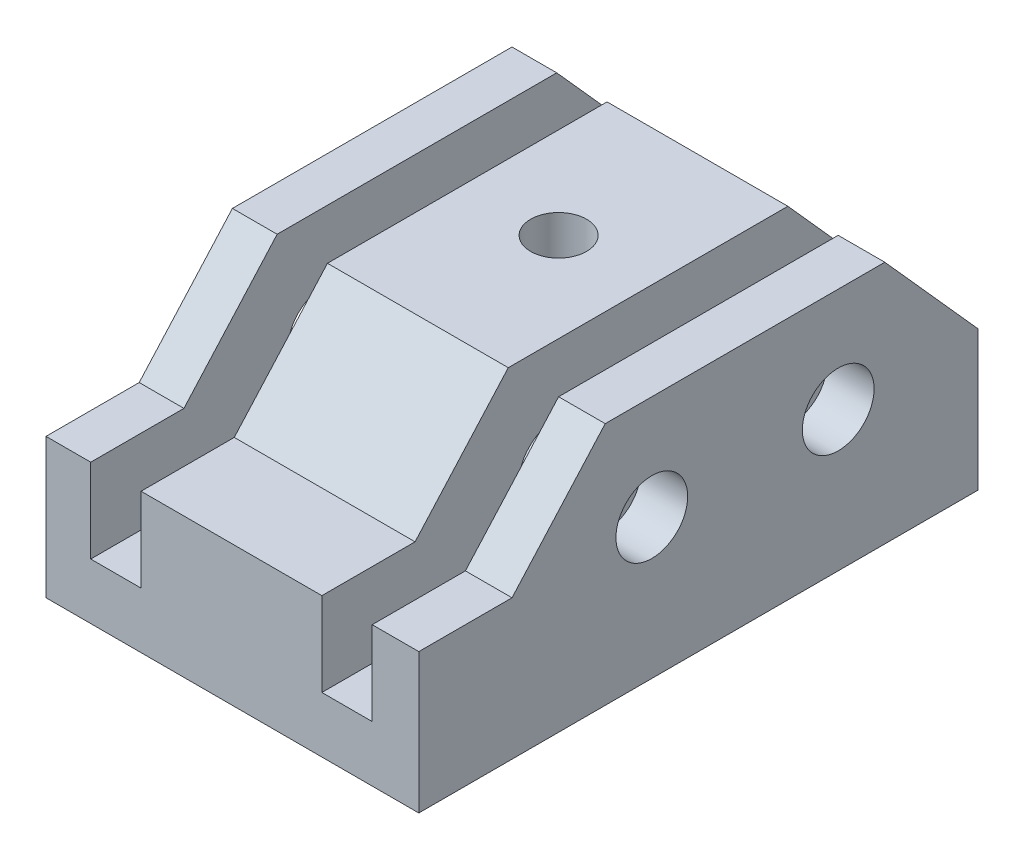
SolidWorks part; units mm, degrees
ref_plane "Front Plane" through (0, 0, 0) normal (0, 0, 1) x (1, 0, 0)
ref_plane "Top Plane" through (0, 0, 0) normal (0, 1, 0) x (1, 0, 0)
ref_plane "Right Plane" through (0, 0, 0) normal (1, 0, 0) x (0, 0, -1)
sketch "Sketch1" plane through (0, 0, 0) normal (1, 0, 0) x (0, 0, -1)
  line L1 (0, 0) -> (63.5, 0)
  line L2 (0, 0) -> (0, 6.35)
  line L3 (0, 6.35) -> (63.5, 6.35)
  line L4 (63.5, 0) -> (63.5, 6.35)
  dimension "D1" = 6.35
  dimension "D2" = 63.5
extrude "Boss-Extrude1" add sketch "Sketch1" against normal blind 50.8
sketch "Sketch2" plane through (0, 0, 0) normal (1, 0, 0) x (0, 0, -1)
  line L0 (0, 6.35) -> (0, 19.05)
  line L1 (0, 19.05) -> (12.7, 33.249)
  line L2 (12.7, 33.249) -> (50.8, 33.249)
  line L3 (50.8, 33.249) -> (63.5, 19.05)
  line L4 (63.5, 19.05) -> (63.5, 6.35)
  line L5 (63.5, 6.35) -> (0, 6.35)
  point P7 (31.75, 33.249)
  point P10 (31.75, 6.35)
  dimension "D1" = 38.1
  dimension "D2" = 12.7
  dimension "D3" = 12.7
  dimension "D4" = 19.05
  dimension "D5" = 19.05
extrude "Boss-Extrude2" add sketch "Sketch2" against normal blind 50.8
sketch "Sketch10" plane through (0, 0, -63.5) normal (0, 0, -1) x (-1, 0, 0)
  line L1 (50.8, 33.249) -> (0, 33.249) construction
  line L3 (6.35, 7.62) -> (6.35, 33.249)
  line L4 (6.35, 33.249) -> (13.208, 33.249)
  line L5 (13.208, 7.62) -> (13.208, 33.249)
  line L6 (6.35, 7.62) -> (13.208, 7.62)
  line L8 (50.8, 0) -> (0, 0) construction
  point P11 (13.208, 7.62)
  dimension "D1" = 7.62
  dimension "D2" = 6.858
  dimension "D3" = 6.35
extrude "Cut-Extrude1" cut sketch "Sketch10" against normal through all
pattern_linear "LPattern3" count 2 spacing 31.496 along (-1, 0, 0) of "Cut-Extrude1"
sketch "Sketch11" plane through (0, 0, 0) normal (1, 0, 0) x (0, 0, -1)
  circle A0 centre (19.05, 19.05) radius 4.8895
  circle A1 centre (19.05, 19.05) radius 7.9375 construction
  circle A2 centre (44.45, 19.05) radius 4.8895
  circle A3 centre (44.45, 19.05) radius 7.9375 construction
  dimension "D1" = 9.779
  dimension "D3" = 15.875
  dimension "D4" = 9.779
  dimension "D6" = 15.875
  dimension "D2" = 6.35
  dimension "D5" = 6.35
extrude "Cut-Extrude2" cut sketch "Sketch11" against normal through all
sketch "Sketch14" plane through (0, 33.249, 0) normal (0, 1, 0) x (1, 0, 0)
  line L3 (-37.846, 12.7) -> (-37.846, 50.8) construction
  point P0 (-25.4, 31.75)
  point P4 (-37.846, 31.75)
  dimension "D1" = 12.446
sketch "Sketch17" plane through (0, 40.0201, -44.7438) normal (0, 0.6667, -0.7454) x (-1, 0, 0)
  line L0 (13.208, -28.1343) -> (13.208, -9.0843) construction
  line L1 (37.846, -9.0843) -> (13.208, -9.0843) construction
  point P0 (25.527, -18.6093)
  point P4 (13.208, -18.6093)
  point P7 (25.527, -9.0843)
sketch "Sketch18" plane through (0, 8.4667, 9.466) normal (0, 0.6667, 0.7454) x (1, 0, 0)
  line L0 (-13.208, 33.249) -> (-13.208, 14.199) construction
  line L1 (-37.846, 33.249) -> (-13.208, 33.249) construction
  point P0 (-25.527, 23.724)
  point P1 (-25.527, 23.724)
  point P4 (-13.208, 23.724)
  point P7 (-25.527, 33.249)
ref_plane "Plane2" through (0, 33.02, 0) normal (0, -1, 0) x (-1, 0, 0)
fillet "Fillet1" [suppressed] radius 2.54
sketch "Sketch22" plane through (0, 0, 0) normal (0, 0, 1) x (1, 0, 0)
  line L0 (-50.8, 19.05) -> (-50.8, 0) construction
  line L1 (0, 0) -> (-50.8, 0)
  line L2 (0, 0) -> (0, 7.62)
  line L3 (-6.35, 7.62) -> (-13.208, 7.62)
  line L4 (-50.8, 0) -> (-50.8, 7.62)
  line L5 (-37.846, 7.62) -> (-37.846, 19.05)
  line L6 (-37.846, 19.05) -> (-13.208, 19.05)
  line L7 (-13.208, 19.05) -> (-13.208, 7.62)
  line L8 (-37.846, 7.62) -> (-44.704, 7.62)
  line L9 (-50.8, 7.62) -> (-50.8, 19.05)
  line L10 (-50.8, 19.05) -> (-44.704, 19.05)
  line L11 (-44.704, 19.05) -> (-44.704, 7.62)
  line L12 (-6.35, 7.62) -> (-6.35, 19.05)
  line L13 (-6.35, 19.05) -> (0, 19.05)
  line L14 (0, 19.05) -> (0, 7.62)
extrude "Boss-Extrude3" add sketch "Sketch22" along normal blind 12.7
sketch "Sketch23" plane through (0, 33.249, 0) normal (0, 1, 0) x (1, 0, 0)
  line L0 (-25.4, 63.5) -> (-25.4, -12.7) construction
  line L1 (-50.8, 63.5) -> (0, 63.5) construction
  line L2 (-50.8, -12.7) -> (0, -12.7) construction
  circle A0 centre (-25.4, 31.75) radius 3.81
  point P15 (-34.579, 50.8)
  dimension "D1" = 7.62
extrude "Cut-Extrude6" cut sketch "Sketch23" against normal through all
sketch "Sketch24" plane through (0, 0, 0) normal (0, -1, 0) x (1, 0, 0)
  line L0 (-25.4, -63.5) -> (-25.4, 12.7) construction
  line L1 (-13.97, -50.8) -> (-36.83, -50.8)
  line L2 (-13.97, -50.8) -> (-13.97, 7.62)
  line L3 (-13.97, 7.62) -> (-36.83, 7.62)
  line L4 (-36.83, -50.8) -> (-36.83, 7.62)
  line L5 (-50.8, -63.5) -> (0, -63.5) construction
  line L6 (-50.8, 12.7) -> (0, 12.7) construction
  line L7 (-25.4, -50.8) -> (-25.4, 7.62) construction
  circle A0 centre (-25.4, -31.75) radius 3.81 construction
  dimension "D1" = 58.42
  dimension "D2" = 19.05
  dimension "D3" = 22.86
extrude "Cut-Extrude7" cut sketch "Sketch24" against normal blind 4.58
sketch "Sketch25" plane through (0, 4.58, 0) normal (0, -1, 0) x (1, 0, 0)
  circle A0 centre (-25.4, -31.75) radius 7
  dimension "D1" = 14
extrude "Cut-Extrude8" cut sketch "Sketch25" against normal blind 2.8
sketch "Sketch26" plane through (0, 4.58, 0) normal (0, -1, 0) x (-1, 0, 0)
  line L0 (25.4, 50.8) -> (25.4, -7.62) construction
  line L1 (36.83, 50.8) -> (13.97, 50.8) construction
  line L2 (13.97, -7.62) -> (36.83, -7.62) construction
  circle A0 centre (30.4, 46.15) radius 3
  circle A1 centre (20.4, 46.15) radius 3
  circle A2 centre (25.4, 31.75) radius 7 construction
  circle A3 centre (20.4, -1.897) radius 3
  circle A4 centre (30.4, -1.897) radius 3
  dimension "D2" = 6
  dimension "D5" = 5
  dimension "D1" = 14.4
  dimension "D3" = 10
  dimension "D4" = 10
extrude "Cut-Extrude9" cut sketch "Sketch26" against normal blind 10
